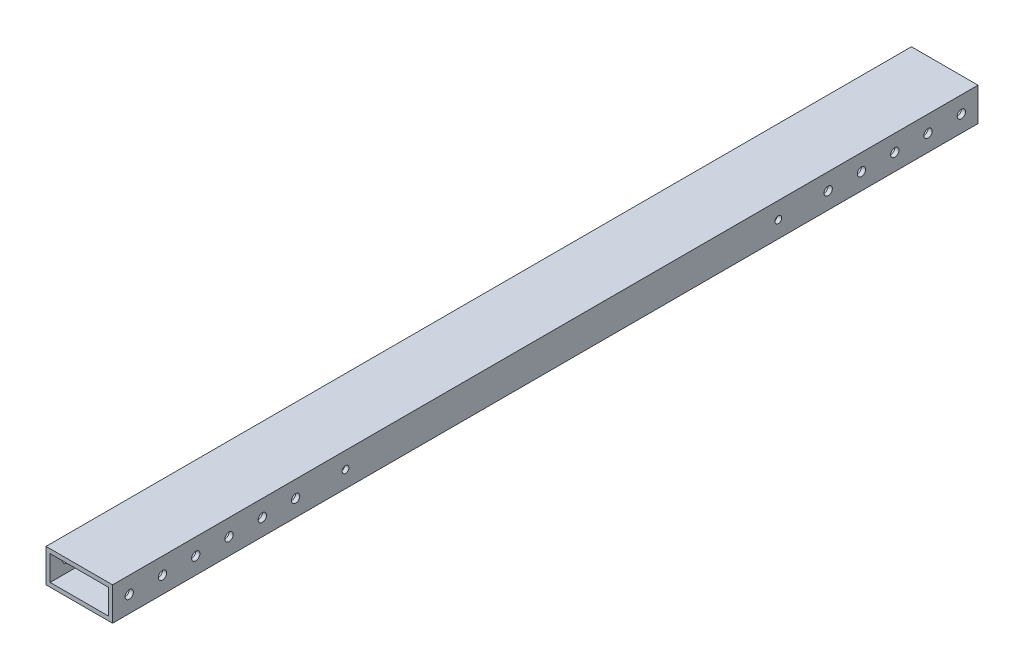
SolidWorks part; units mm, degrees
material "6061 Alloy"
ref_plane "Front Plane" through (0, 0, 0) normal (0, 0, 1) x (1, 0, 0)
ref_plane "Top Plane" through (0, 0, 0) normal (0, 1, 0) x (1, 0, 0)
ref_plane "Right Plane" through (0, 0, 0) normal (1, 0, 0) x (0, 0, -1)
sketch "Sketch1" plane through (0, 0, 0) normal (0, 0, 1) x (1, 0, 0)
  line L0 (-22.225, 9.525) -> (22.225, 9.525)
  line L2 (-25.4, 12.7) -> (25.4, 12.7)
  line L3 (-25.4, 12.7) -> (-25.4, -12.7)
  line L4 (-25.4, -12.7) -> (25.4, -12.7)
  line L5 (25.4, 12.7) -> (25.4, -12.7)
  line L10 (22.225, 9.525) -> (22.225, -9.525)
  line L11 (-22.225, -9.525) -> (22.225, -9.525)
  line L12 (-22.225, 9.525) -> (-22.225, -9.525)
  point P12 (0, 12.7)
  point P14 (25.4, 0)
  dimension "Wall Thickness" = 3.175
  dimension "Outside Width" = 50.8
  dimension "Outside Height" = 25.4
  dimension "Inside Height" = 19.05
  dimension "Inside Width" = 44.45
sketch "Sketch2" plane through (0, 0, 0) normal (1, 0, 0) x (0, 0, -1)
  line L0 (330.2, 0) -> (-330.2, 0)
  point P4 (0, 0)
  point P7 (-330.2, 0)
  point P10 (330.2, 0)
  dimension "Length" = 660.4
sketch "Sketch3" plane through (0, 0, 0) normal (0, 0, 1) x (1, 0, 0)
  line L21 (25.4, 12.7) -> (-25.4, 12.7)
  line L22 (25.4, -12.7) -> (25.4, 12.7)
  line L23 (-25.4, -12.7) -> (25.4, -12.7)
  line L24 (-25.4, 12.7) -> (-25.4, -12.7)
  line L25 (25.4, 12.7) -> (-25.4, 12.7)
  line L26 (25.4, -12.7) -> (25.4, 12.7)
  line L27 (-25.4, -12.7) -> (25.4, -12.7)
  line L28 (-25.4, 12.7) -> (-25.4, -12.7)
  line L29 (22.225, 9.525) -> (-22.225, 9.525)
  line L30 (22.225, -9.525) -> (22.225, 9.525)
  line L31 (-22.225, -9.525) -> (22.225, -9.525)
  line L32 (-22.225, 9.525) -> (-22.225, -9.525)
  line L33 (22.225, 9.525) -> (-22.225, 9.525)
  line L34 (22.225, -9.525) -> (22.225, 9.525)
  line L35 (-22.225, -9.525) -> (22.225, -9.525)
  line L36 (-22.225, 9.525) -> (-22.225, -9.525)
  dimension "D1" = 0
  dimension "D2" = 0
extrude "Boss-Extrude1" add sketch "Sketch3" along normal up to vertex (330.2 mm away) and the other way up to vertex (330.2 mm away) up to point (0, 0, 330.2) other way up to point (0, 0, -330.2)
sketch "Drawing Reference" plane through (0, 0, 0) normal (1, 0, 0) x (0, 0, -1)
  line L0 (-330.2, 0) -> (330.2, 0) construction
  line L1 (0, -12.7) -> (0, 12.7) construction
  line L2 (-330.2, -12.7) -> (330.2, -12.7) construction
  line L5 (-330.2, 12.7) -> (330.2, 12.7) construction
  point P7 (-293.624, 0)
  point P8 (293.624, 0)
  dimension "D1" = 36.576
sketch "Sketch5" plane through (25.4, 0, 0) normal (1, 0, 0) x (0, 0, -1)
  line L2 (-266.7, 0) -> (-241.3, 0)
  line L3 (-241.3, 0) -> (-215.9, 0)
  line L4 (-215.9, 0) -> (-190.5, 0)
  line L5 (-317.5, 0) -> (-330.2, 0)
  line L6 (-330.2, -12.7) -> (-330.2, 12.7) construction
  line L7 (-317.5, 0) -> (-292.1, 0)
  line L8 (-292.1, 0) -> (-266.7, 0)
sketch "Sketch8" plane through (25.4, 0, 0) normal (1, 0, 0) x (0, 0, -1)
  line L0 (330.2, 0) -> (292.1, 0)
  line L1 (330.2, -12.7) -> (330.2, 12.7) construction
  line L2 (292.1, 0) -> (266.7, 0)
  line L3 (266.7, 0) -> (241.3, 0)
  line L4 (241.3, 0) -> (215.9, 0)
  line L5 (330.2, 0) -> (317.5, 0)
hole_wizard "1/4 (0.25) Diameter Hole3" positions "Sketch12" profile "Sketch13" hole size "1/4" standard "ANSI Inch" end condition through all
sketch "Sketch12" plane through (-25.4, 0, 0) normal (-1, 0, 0) x (0, 0, 1)
  point P4 (-317.5, 0)
sketch "Sketch13" plane through (-25.4, 0, -317.5) normal (0, 1, 0) x (0, 0, 1)
  line L0 (0, 0) -> (0, 50.8)
  line L1 (0, 50.8) -> (3.175, 50.8)
  line L2 (3.175, 50.8) -> (3.175, 0)
  line L5 (3.175, 0) -> (0, 0)
  line L11 (0, -6.35) -> (0, 107.95) construction
  dimension "Thru Hole Dia." = 6.35
  dimension "Thru Hole Depth" = 50.8
hole_wizard "1/4 (0.25) Diameter Hole4" positions "Sketch14" profile "Sketch15" hole size "1/4" standard "ANSI Inch" end condition through all
sketch "Sketch14" plane through (-25.4, 0, 0) normal (-1, 0, 0) x (0, 0, 1)
  point P0 (292.1, 0)
  point P3 (317.5, 0)
  point P6 (292.1, 0)
  point P8 (317.5, 0)
sketch "Sketch15" plane through (-25.4, 0, 292.1) normal (0, 1, 0) x (0, 0, 1)
  line L0 (0, 0) -> (0, 50.8)
  line L1 (0, 50.8) -> (3.175, 50.8)
  line L2 (3.175, 50.8) -> (3.175, 0)
  line L5 (3.175, 0) -> (0, 0)
  line L11 (0, -6.35) -> (0, 107.95) construction
  dimension "Thru Hole Dia." = 6.35
  dimension "Thru Hole Depth" = 50.8
hole_wizard "1/4 (0.25) Diameter Hole5" positions "Sketch17" profile "Sketch18" hole size "1/4" standard "ANSI Inch" end condition through all
sketch "Sketch17" plane through (25.4, 0, 0) normal (1, 0, 0) x (0, 0, -1)
  point P0 (292.1, 0)
  point P3 (266.7, 0)
sketch "Sketch18" plane through (25.4, 0, -292.1) normal (0, 1, 0) x (0, 0, -1)
  line L0 (0, 0) -> (0, 50.8)
  line L1 (0, 50.8) -> (3.175, 50.8)
  line L2 (3.175, 50.8) -> (3.175, 0)
  line L5 (3.175, 0) -> (0, 0)
  line L11 (0, -6.35) -> (0, 107.95) construction
  dimension "Thru Hole Dia." = 6.35
  dimension "Thru Hole Depth" = 50.8
hole_wizard "1/4 (0.25) Diameter Hole6" positions "Sketch19" profile "Sketch20" hole size "1/4" standard "ANSI Inch" end condition through all
sketch "Sketch19" plane through (25.4, 0, 0) normal (1, 0, 0) x (0, 0, -1)
  point P0 (215.9, 0)
  point P3 (241.3, 0)
sketch "Sketch20" plane through (25.4, 0, -215.9) normal (0, 1, 0) x (0, 0, -1)
  line L0 (0, 0) -> (0, 50.8)
  line L1 (0, 50.8) -> (3.175, 50.8)
  line L2 (3.175, 50.8) -> (3.175, 0)
  line L5 (3.175, 0) -> (0, 0)
  line L11 (0, -6.35) -> (0, 107.95) construction
  dimension "Thru Hole Dia." = 6.35
  dimension "Thru Hole Depth" = 50.8
hole_wizard "1/4 (0.25) Diameter Hole7" positions "Sketch21" profile "Sketch22" hole size "1/4" standard "ANSI Inch" end condition through all
sketch "Sketch21" plane through (25.4, 0, 0) normal (1, 0, 0) x (0, 0, -1)
  point P0 (-190.5, 0)
  point P3 (-215.9, 0)
sketch "Sketch22" plane through (25.4, 0, 190.5) normal (0, 1, 0) x (0, 0, -1)
  line L0 (0, 0) -> (0, 50.8)
  line L1 (0, 50.8) -> (3.175, 50.8)
  line L2 (3.175, 50.8) -> (3.175, 0)
  line L5 (3.175, 0) -> (0, 0)
  line L11 (0, -6.35) -> (0, 107.95) construction
  dimension "Thru Hole Dia." = 6.35
  dimension "Thru Hole Depth" = 50.8
hole_wizard "1/4 (0.25) Diameter Hole8" positions "Sketch23" profile "Sketch24" hole size "1/4" standard "ANSI Inch" end condition through all
sketch "Sketch23" plane through (25.4, 0, 0) normal (1, 0, 0) x (0, 0, -1)
  point P0 (-266.7, 0)
  point P3 (-241.3, 0)
sketch "Sketch24" plane through (25.4, 0, 266.7) normal (0, 1, 0) x (0, 0, -1)
  line L0 (0, 0) -> (0, 50.8)
  line L1 (0, 50.8) -> (3.175, 50.8)
  line L2 (3.175, 50.8) -> (3.175, 0)
  line L5 (3.175, 0) -> (0, 0)
  line L11 (0, -6.35) -> (0, 107.95) construction
  dimension "Thru Hole Dia." = 6.35
  dimension "Thru Hole Depth" = 50.8
sketch "Sketch25" plane through (25.4, 0, 0) normal (1, 0, 0) x (0, 0, -1)
  line L0 (-190.5, 0) -> (-152.4, 0)
  line L1 (215.9, 0) -> (177.8, 0)
hole_wizard "13/64 (0.20313) Diameter Hole1" positions "Sketch26" profile "Sketch27" hole size "13/64" standard "ANSI Inch" end condition through all
sketch "Sketch26" plane through (25.4, 0, 0) normal (1, 0, 0) x (0, 0, -1)
  point P0 (-152.4, 0)
  point P3 (177.8, 0)
sketch "Sketch27" plane through (25.4, 0, 152.4) normal (0, 1, 0) x (0, 0, -1)
  line L0 (0, 0) -> (0, 50.8)
  line L1 (0, 50.8) -> (2.5798, 50.8)
  line L2 (2.5798, 50.8) -> (2.5798, 0)
  line L5 (2.5798, 0) -> (0, 0)
  line L11 (0, -6.35) -> (0, 107.95) construction
  dimension "Thru Hole Dia." = 5.1595
  dimension "Thru Hole Depth" = 50.8
sketch "Sketch28" plane through (-25.4, 0, 0) normal (-1, 0, 0) x (0, 0, 1)
  line L0 (103.1875, 0) -> (77.7875, 0)
  line L1 (-103.1875, 0) -> (-128.5875, 0)
hole_wizard "1/2 (0.5) Diameter Hole1" positions "Sketch29" profile "Sketch30" hole size "1/2" standard "ANSI Inch"
sketch "Sketch29" plane through (-25.4, 0, 0) normal (-1, 0, 0) x (0, 0, 1)
  point P1 (-591.3016, -480.8022)
  point P3 (-103.1875, 0)
  point P6 (77.7875, 0)
  point P9 (103.1875, 0)
  point P13 (-128.5875, 0)
sketch "Sketch30" plane through (-25.4, -480.8022, -591.3016) normal (0, 1, 0) x (0, 0, 1)
  line L0 (0, 0) -> (0, 10.1655)
  line L1 (0, 10.1655) -> (6.35, 6.35)
  line L2 (6.35, 6.35) -> (6.35, 0)
  line L5 (6.35, 0) -> (0, 0)
  line L10 (0, 10.1655) -> (-6.35, 6.35) construction
  line L11 (0, -6.35) -> (0, 107.95) construction
  dimension "Hole Dia." = 12.7
  dimension "Hole Depth" = 6.35
  dimension "Drill Angle" = 118
equation "\"D1@Drawing Reference\"=\"Outside Width@Sketch1\" * 0.72"
